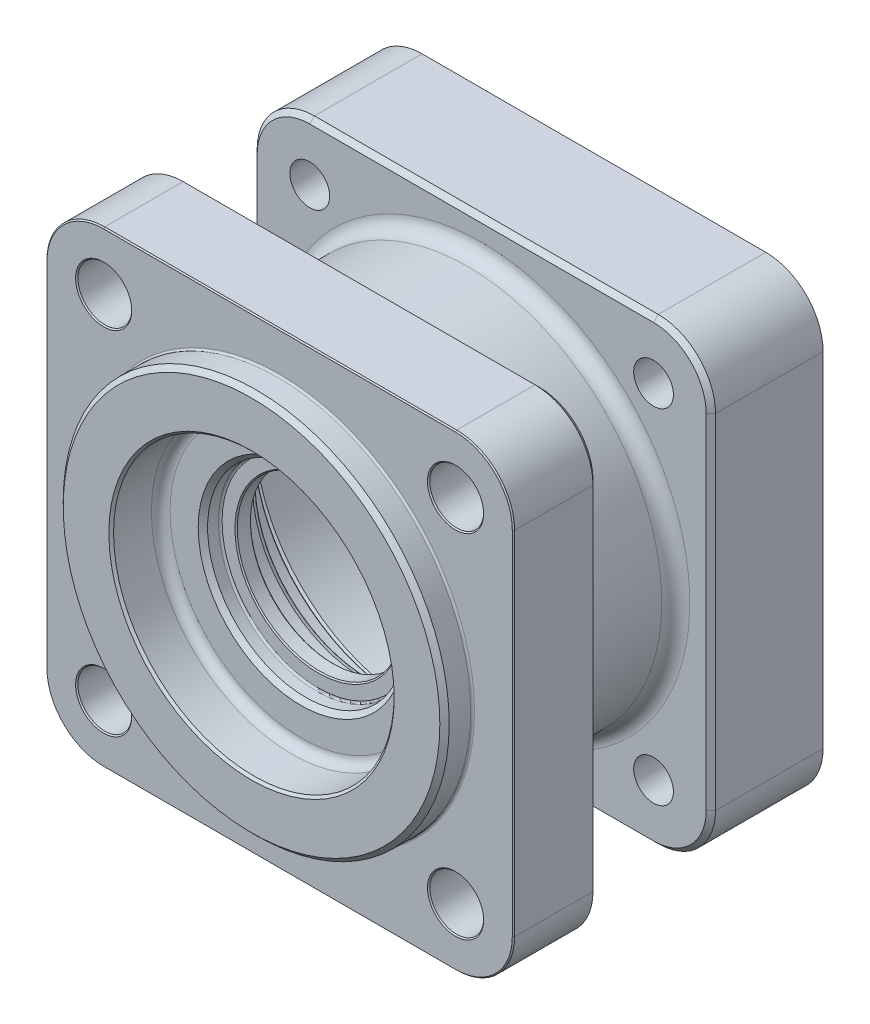
SolidWorks part; units mm, degrees
material "4140 H-T"
ref_plane "Front Plane" through (0, 0, 0) normal (0, 0, 1) x (1, 0, 0)
ref_plane "Top Plane" through (0, 0, 0) normal (0, 1, 0) x (1, 0, 0)
ref_plane "Right Plane" through (0, 0, 0) normal (1, 0, 0) x (0, 0, -1)
sketch "Sketch1" plane through (0, 0, 0) normal (1, 0, 0) x (0, 0, -1)
  line L0 (0, 0) -> (127.7158, 0) construction
  line L1 (0, 30.5) -> (0, 40.26)
  line L2 (6, 67.5) -> (24, 67.5)
  line L3 (24, 67.5) -> (24, 41.5)
  line L4 (24, 41.5) -> (49.2, 41.5)
  line L5 (49.2, 41.5) -> (49.2, 67.5)
  line L6 (49.2, 67.5) -> (73.2, 67.5)
  line L7 (73.2, 67.5) -> (73.2, 37.375)
  line L8 (73.2, 37.375) -> (71.4, 37.375)
  line L9 (70.9, 36.875) -> (70.9, 34.5)
  line L10 (70.4, 34) -> (34.7, 34)
  line L11 (32.7, 33.7691) -> (32.7, 32.25)
  line L12 (32.45, 32) -> (26, 32)
  line L13 (25.2, 31.2) -> (25.2, 24.6516)
  line L14 (24.2, 24) -> (18.4, 24)
  line L15 (17.6, 23.2) -> (17.6, 17.85)
  line L16 (13.9, 21) -> (11.6, 21)
  line L17 (10.6, 22) -> (10.6, 28)
  line L18 (8.6, 30) -> (0.5, 30)
  line L19 (1, 41.26) -> (5.6, 41.26)
  line L20 (6, 41.66) -> (6, 67.5)
  line L21 (34.7, 34) -> (33.9, 34.4619)
  line L22 (32.7, 32.25) -> (32.45, 32)
  line L23 (24.2, 24) -> (24.8294, 24.1686)
  line L24 (17.35, 17.6) -> (17.6, 17.85)
  line L25 (11.6, 21) -> (10.6, 22)
  line L26 (0.5, 30) -> (0, 30.5)
  line L27 (0, 40.26) -> (1, 41.26)
  line L28 (14.3, 20.6) -> (14.3, 17.85)
  line L29 (14.55, 17.6) -> (17.35, 17.6)
  line L30 (14.3, 17.85) -> (14.55, 17.6)
  arc A0 (33.9, 34.4619) -> (32.7, 33.7691) centre (33.5, 33.7691) ccw
  arc A1 (26, 32) -> (25.2, 31.2) centre (26, 31.2) ccw
  arc A2 (18.4, 24) -> (17.6, 23.2) centre (18.4, 23.2) ccw
  arc A3 (70.9, 34.5) -> (70.4, 34) centre (70.4, 34.5) cw
  arc A4 (71.4, 37.375) -> (70.9, 36.875) centre (71.4, 36.875) ccw
  arc A5 (14.3, 20.6) -> (13.9, 21) centre (13.9, 20.6) ccw
  arc A6 (25.2, 24.6516) -> (24.8294, 24.1686) centre (24.7, 24.6516) cw
  arc A7 (10.6, 28) -> (8.6, 30) centre (8.6, 28) ccw
  arc A8 (5.6, 41.26) -> (6, 41.66) centre (5.6, 41.66) ccw
  point P3 (10.6, 21)
  point P8 (14.3, 17.6)
  point P15 (32.7, 32)
  point P19 (17.6, 21)
  point P20 (0, 41.26)
  point P22 (0, 30)
  point P57 (17.6, 17.6)
  dimension "D17" = 0.8
  dimension "D24" = 0.8
  dimension "D25" = 0.5
  dimension "D26" = 35.2
  dimension "D27" = 2
  dimension "D38" = 0.4
  dimension "D39" = 0.4
  dimension "D22" = 0.5
  dimension "D1" = 74.75
  dimension "D2" = 2.3
  dimension "D3" = 68
  dimension "D4" = 40.5
  dimension "D5" = 48
  dimension "D6" = 55.6
  dimension "D7" = 42
  dimension "D8" = 60
  dimension "D9" = 10.6
  dimension "D10" = 82.52
  dimension "D11" = 6
  dimension "D12" = 67.2
  dimension "D13" = 18
  dimension "D14" = 24
  dimension "D15" = 83
  dimension "D16" = 135
  dimension "D18" = 30
  dimension "D19" = 2
  dimension "D20" = 0.25
  dimension "D21" = 45
  dimension "D23" = 15
  dimension "D28" = 14.3
  dimension "D30" = 1
  dimension "D31" = 45
  dimension "D32" = 0.5
  dimension "D33" = 45
  dimension "D34" = 1
  dimension "D35" = 45
  dimension "D36" = 64
  dimension "D37" = 48
  dimension "D40" = 1
revolve "Revolve1" add sketch "Sketch1" angle 360 about L0
sketch "Sketch2" plane through (0, 0, -73.2) normal (0, 0, -1) x (-1, 0, 0)
  line L0 (0, 0) -> (80.2716, 0) construction
  line L1 (0, 0) -> (0, 68.516) construction
  line L2 (36.75, 49) -> (-36.75, 49)
  line L3 (49, 36.75) -> (49, -36.75)
  line L4 (-49, 36.75) -> (-49, -36.75)
  line L5 (36.75, -49) -> (-36.75, -49)
  circle A0 centre (-36.75, 36.75) radius 4.25
  circle A1 centre (36.75, 36.75) radius 4.25
  circle A2 centre (36.75, -36.75) radius 4.25
  circle A3 centre (-36.75, -36.75) radius 4.25
  arc A4 (49, 36.75) -> (36.75, 49) centre (36.75, 36.75) ccw
  arc A5 (-36.75, 49) -> (-49, 36.75) centre (-36.75, 36.75) ccw
  arc A6 (-49, -36.75) -> (-36.75, -49) centre (-36.75, -36.75) ccw
  arc A7 (36.75, -49) -> (49, -36.75) centre (36.75, -36.75) ccw
  dimension "D1" = 73.5
  dimension "D2" = 73.5
  dimension "D3" = 8.5
  dimension "D4" = 98
extrude "Cut-Extrude1" cut sketch "Sketch2" against normal up to surface (24 mm away) flip side to cut up to face at (41.5, 0, -49.2)
cosmetic thread "Cosmetic Thread1" parameters "D2"=10
cosmetic thread "Cosmetic Thread2" parameters "D2"=10
cosmetic thread "Cosmetic Thread3" parameters "D2"=10
cosmetic thread "Cosmetic Thread4" parameters "D2"=10
sketch "Sketch3" plane through (0, 0, -6) normal (0, 0, 1) x (1, 0, 0)
  line L0 (0, 0) -> (76.3341, 0) construction
  line L1 (0, 0) -> (0, 74.6686) construction
  line L2 (-37.6181, 50) -> (37.6181, 50)
  line L3 (50, 37.6181) -> (50, -37.6181)
  line L4 (37.6181, -50) -> (-37.6181, -50)
  line L5 (-50, -37.6181) -> (-50, 37.6181)
  line L6 (37.6181, 37.6181) -> (0, 0) construction
  circle A0 centre (37.6181, 37.6181) radius 5.75
  circle A1 centre (-37.6181, 37.6181) radius 5.75
  circle A2 centre (-37.6181, -37.6181) radius 5.75
  circle A3 centre (37.6181, -37.6181) radius 5.75
  arc A4 (50, 37.6181) -> (37.6181, 50) centre (37.6181, 37.6181) ccw
  arc A5 (-37.6181, 50) -> (-50, 37.6181) centre (-37.6181, 37.6181) ccw
  arc A6 (-50, -37.6181) -> (-37.6181, -50) centre (-37.6181, -37.6181) ccw
  arc A7 (37.6181, -50) -> (50, -37.6181) centre (37.6181, -37.6181) ccw
  circle A8 centre (0, 0) radius 53.2 construction
  dimension "D1" = 106.4
  dimension "D2" = 45
  dimension "D3" = 11.5
  dimension "D5" = 75.2362
  dimension "D6" = 75.2362
  dimension "D4" = 100
extrude "Cut-Extrude2" cut sketch "Sketch3" against normal up to surface (18 mm away) flip side to cut up to face at (67.5, 0, -24)
sketch "Sketch4" plane through (0, 0, -73.2) normal (0, 0, -1) x (-1, 0, 0)
  circle A0 centre (-36.75, 36.75) radius 5.5
  circle A1 centre (36.75, 36.75) radius 5.5
  circle A2 centre (-36.75, -36.75) radius 5.5
  circle A3 centre (36.75, -36.75) radius 5.5
  dimension "D1" = 11
extrude "Cut-Extrude3" cut sketch "Sketch4" against normal blind 2
fillet "Fillet4" radius 0.8 1 edges at (41.5, 0, -24)
fillet "Fillet5" radius 3 1 edges at (41.5, 0, -49.2)
chamfer "Chamfer1" distance 1 angle 45 16 edges at (-50, 0, -24) (-46.3734, 46.3734, -24) (-46.3734, -46.3734, -24) (0, 50, -24) (0, -50, -24) (46.3734, 46.3734, -24) (46.3734, -46.3734, -24) (50, 0, -24) (-49, 0, -49.2) (-45.4121, -45.4121, -49.2) (-45.4121, 45.4121, -49.2) (0, -49, -49.2) (0, 49, -49.2) (45.4121, -45.4121, -49.2) (45.4121, 45.4121, -49.2) (49, 0, -49.2)
chamfer "Chamfer2" distance 0.25 angle 45 12 edges at (-46.3734, 46.3734, -6) (0, 50, -6) (46.3734, 46.3734, -6) (50, 0, -6) (46.3734, -46.3734, -6) (0, -50, -6) (-46.3734, -46.3734, -6) (-50, 0, -6) (31.8681, -37.6181, -6) (-31.8681, -37.6181, -6) (-43.3681, 37.6181, -6) (43.3681, 37.6181, -6)
